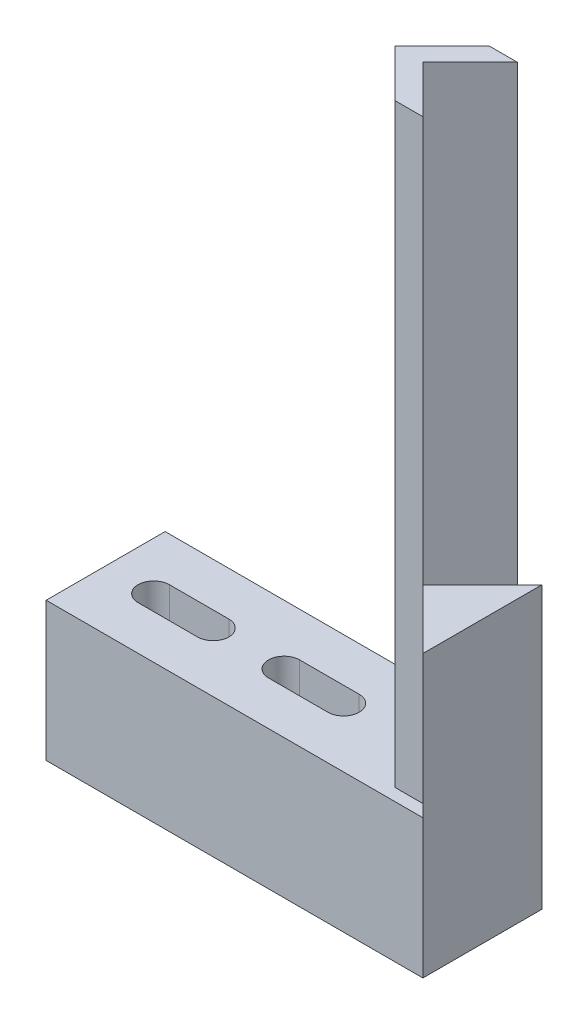
SolidWorks part; units mm, degrees
ref_plane "Front Plane" through (0, 0, 0) normal (0, 0, 1) x (1, 0, 0)
ref_plane "Top Plane" through (0, 0, 0) normal (0, 1, 0) x (1, 0, 0)
ref_plane "Right Plane" through (0, 0, 0) normal (1, 0, 0) x (0, 0, -1)
sketch "Sketch1" plane through (0, 0, 0) normal (0, 0, 1) x (1, 0, 0)
  line L0 (0, 0) -> (48.26, 0)
  line L6 (0, 0) -> (0, 17.78)
  line L10 (0, 17.78) -> (48.26, 17.78)
  line L11 (48.26, 0) -> (48.26, 17.78)
  dimension "D1" = 48.26
  dimension "D2" = 17.78
extrude "Boss-Extrude1" add sketch "Sketch1" against normal blind 15.24
sketch "Sketch3" plane through (0, 17.78, 0) normal (0, 1, 0) x (1, 0, 0)
  line L0 (48.26, 15.24) -> (40.64, 7.62)
  line L1 (40.64, 7.62) -> (48.26, 0)
  line L2 (43.0937, 13.6658) -> (37.0479, 7.62)
  line L4 (48.26, 15.24) -> (48.26, 0)
  line L5 (37.0479, 7.62) -> (43.0937, 1.5742)
  line L9 (43.0937, 13.6658) -> (46.6858, 13.6658)
  line L11 (43.0937, 1.5742) -> (46.6858, 1.5742)
  line L12 (48.26, 0) -> (0, 0) construction
  line L13 (48.26, 15.24) -> (0, 15.24) construction
  line M1 (0, 0) -> (48.26, 0)
  line M2 (48.26, 0) -> (48.26, 15.24)
  line M3 (48.26, 15.24) -> (0, 15.24)
  dimension "D1" = 90
  dimension "D2" = 90
  dimension "D3" = 8.55
  dimension "D4" = 8.55
  dimension "D6" = 2.54
sketch "Sketch4" plane through (0, 17.78, 0) normal (0, 1, 0) x (1, 0, 0)
  line L0 (30.48, 7.62) -> (22.86, 7.62) construction
  line L1 (30.48, 5.62) -> (22.86, 5.62)
  line L2 (30.48, 9.62) -> (22.86, 9.62)
  line L3 (13.78, 7.62) -> (6.16, 7.62) construction
  line L4 (13.78, 5.62) -> (6.16, 5.62)
  line L5 (13.78, 9.62) -> (6.16, 9.62)
  line L6 (48.26, 0) -> (0, 0) construction
  line L7 (48.26, 15.24) -> (48.26, 0) construction
  arc A0 (30.48, 5.62) -> (30.48, 9.62) centre (30.48, 7.62) ccw
  arc A1 (22.86, 9.62) -> (22.86, 5.62) centre (22.86, 7.62) ccw
  arc A2 (13.78, 5.62) -> (13.78, 9.62) centre (13.78, 7.62) ccw
  arc A3 (6.16, 9.62) -> (6.16, 5.62) centre (6.16, 7.62) ccw
  point P2 (26.67, 7.62)
  point P7 (9.97, 7.62)
  point P14 (32.48, 7.62)
  point P16 (4.16, 7.62)
  point P18 (15.78, 7.62)
  point P19 (20.86, 7.62)
  dimension "D1" = 4
  dimension "D2" = 17.78
  dimension "D3" = 7.62
  dimension "D4" = 7.62
  dimension "D5" = 5.08
extrude "Cut-Extrude2" cut sketch "Sketch4" against normal through all
extrude "Boss-Extrude2" add sketch "Sketch3" along normal blind 76.2 contours L2 L5 L1 L0 M1 M3 region at (43.5535, 17.78, -10.7522)
extrude "Boss-Extrude4" add sketch "Sketch3<7>" along normal blind 18.22 contours L0 L1 M2 region at (45.72, 17.78, -7.62)
sketch "Sketch3<7>" plane through (0, 17.78, 0) normal (0, 1, 0) x (1, 0, 0) same geometry as "Sketch3"
